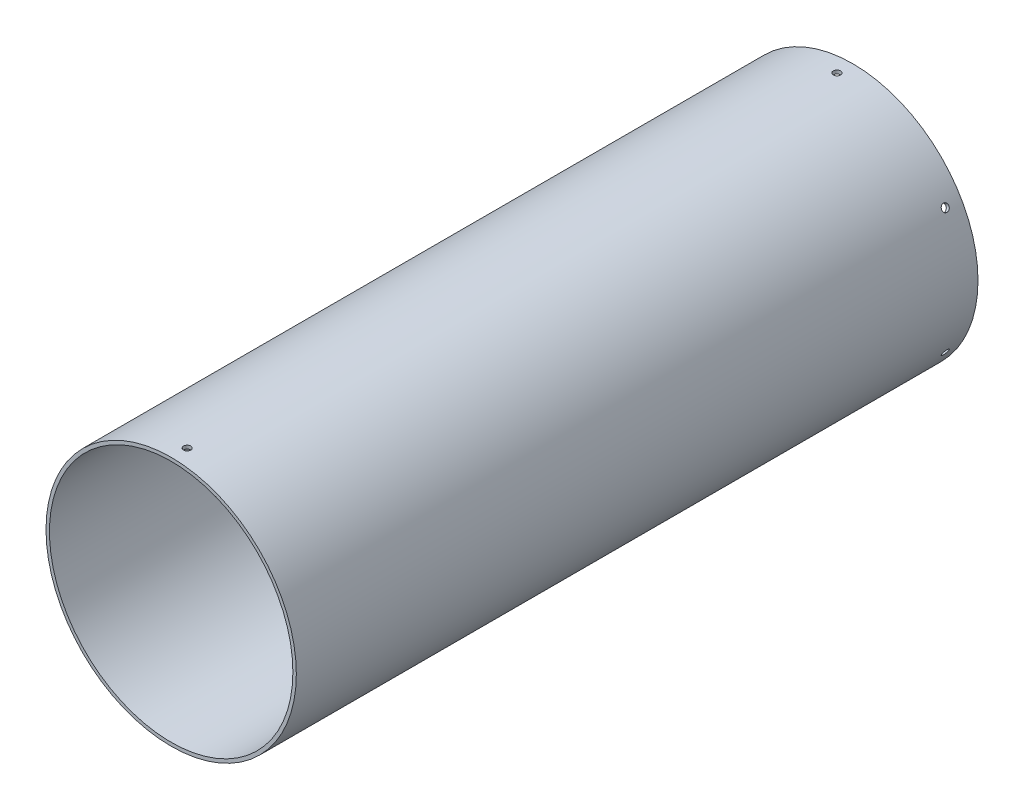
SolidWorks part; units mm, degrees
material "A-Glass Fiber"
ref_plane "Front Plane" through (0, 0, 0) normal (0, 0, 1) x (1, 0, 0)
ref_plane "Top Plane" through (0, 0, 0) normal (0, 1, 0) x (1, 0, 0)
ref_plane "Right Plane" through (0, 0, 0) normal (1, 0, 0) x (0, 0, -1)
sketch "Sketch1" plane through (0, 0, 0) normal (0, 0, 1) x (1, 0, 0)
  circle A0 centre (0, 0) radius 76.2
  circle A1 centre (0, 0) radius 78.359
  dimension "D1" = 156.718
  dimension "D2" = 152.4
extrude "Boss-Extrude1" add sketch "Sketch1" along normal blind 426.75
sketch "Sketch4" plane through (0, 0, 0) normal (0, 1, 0) x (1, 0, 0)
  line L0 (78.359, 0) -> (-78.359, 0) construction
  point P0 (0, -10)
  dimension "D1" = 10
hole_wizard "M4 Clearance Hole2" positions "Sketch4" profile "Sketch5" hole size "M4" standard "ANSI Metric" end condition through all
sketch "Sketch5" plane through (0, 0, 10) normal (1, 0, 0) x (0, 0, 1)
  line L0 (0, 0) -> (0, 78.359)
  line L1 (0, 78.359) -> (2.25, 78.359)
  line L2 (2.25, 78.359) -> (2.25, 0)
  line L5 (2.25, 0) -> (0, 0)
  line L11 (0, -6.35) -> (0, 107.95) construction
  dimension "Thru Hole Dia." = 4.5
  dimension "Thru Hole Depth" = 78.359
pattern_circular "CirPattern1" count 6 over 360 about axis through (0, 0, 426.75) along (0, 0, -1) of "M4 Clearance Hole2" reverse direction yes
sketch "Sketch6" plane through (0, 0, 0) normal (0, 1, 0) x (1, 0, 0)
  line L0 (-78.359, -426.75) -> (78.359, -426.75) construction
  point P0 (0, -416.75)
  dimension "D1" = 10
hole_wizard "M4 Clearance Hole3" positions "Sketch6" profile "Sketch7" hole size "M4" standard "ANSI Metric" end condition through all
sketch "Sketch7" plane through (0, 0, 416.75) normal (1, 0, 0) x (0, 0, -1)
  line L0 (0, 0) -> (0, 78.359)
  line L1 (0, 78.359) -> (2.25, 78.359)
  line L2 (2.25, 78.359) -> (2.25, 0)
  line L5 (2.25, 0) -> (0, 0)
  line L11 (0, -6.35) -> (0, 107.95) construction
  dimension "Thru Hole Dia." = 4.5
  dimension "Thru Hole Depth" = 78.359
